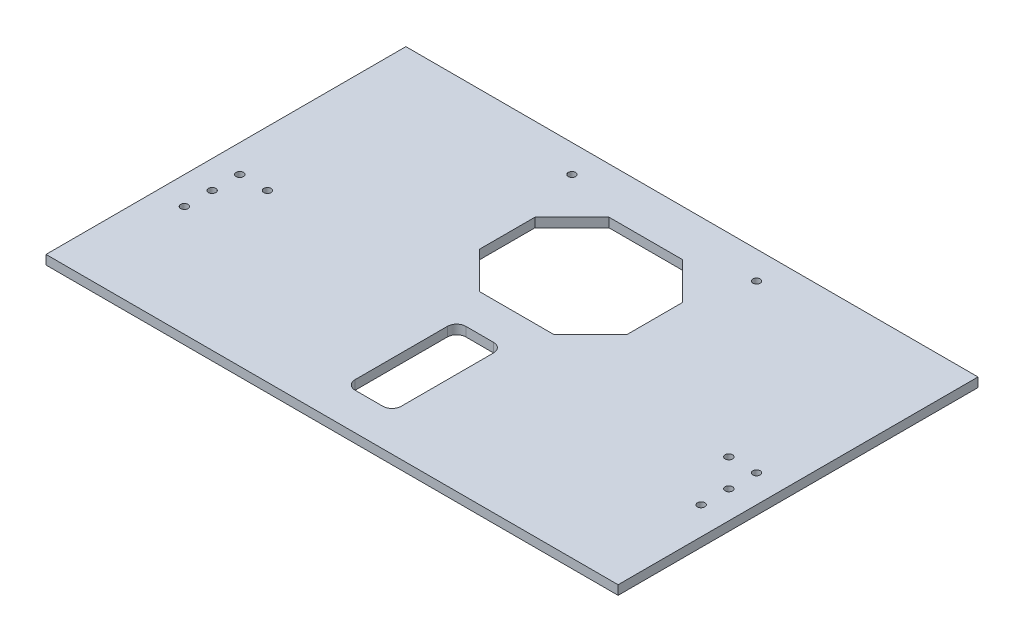
SolidWorks part; units mm, degrees
ref_plane "前视基准面" through (0, 0, 0) normal (0, 0, 1) x (1, 0, 0)
ref_plane "上视基准面" through (0, 0, 0) normal (0, 1, 0) x (1, 0, 0)
ref_plane "右视基准面" through (0, 0, 0) normal (1, 0, 0) x (0, 0, -1)
sketch "Sketch1" plane through (0, 0, 0) normal (0, 1, 0) x (1, 0, 0)
  line L0 (0, 50) -> (0, 97.5) construction
  line L1 (-155, 50) -> (155, 50)
  line L2 (-155, 50) -> (-155, -50)
  line L3 (-155, -50) -> (155, -50)
  line L4 (155, 50) -> (155, -50)
  line L5 (-155, 50) -> (155, -50) construction
  line L6 (-155, -50) -> (155, 50) construction
  line L8 (-60, 145) -> (60, 145)
  line L9 (-60, 145) -> (-60, 50)
  line L10 (-60, 50) -> (60, 50)
  line L11 (60, 145) -> (60, 50)
  line L12 (-60, 145) -> (60, 50) construction
  line L13 (-60, 50) -> (60, 145) construction
  point P0 (0, 0)
  dimension "D1" = 310
  dimension "100" = 100
  dimension "D2" = 120
  dimension "D3" = 95
extrude "Boss-Extrude1" add sketch "Sketch1" along normal blind 5 contours L11 L8 L9 L1 | L4 L1 L2 L3 region at (0, 0, 0) region at (0, 0, -97.5)
sketch "Sketch2" plane through (0, 5, 0) normal (0, 1, 0) x (1, 0, 0)
  line L0 (-140, -50) -> (-140, 50) construction
  line L1 (-155, -50) -> (155, -50) construction
  line L2 (-155, 50) -> (-60, 50) construction
  line L3 (0, 0) -> (0, 145) construction
  line L4 (-60, 145) -> (60, 145) construction
  line L5 (-155, 50) -> (-155, -50) construction
  line L6 (-155, 40) -> (155, 40) construction
  line L7 (-12.5, -30) -> (12.5, -30)
  line L8 (-12.5, -30) -> (-12.5, 30)
  line L9 (-12.5, 30) -> (12.5, 30)
  line L10 (12.5, -30) -> (12.5, 30)
  line L11 (-12.5, -30) -> (12.5, 30) construction
  line L12 (-12.5, 30) -> (12.5, -30) construction
  line L13 (-50, 145) -> (-50, 40) construction
  line L14 (-60, 145) -> (-60, 50) construction
  line L15 (140, -50) -> (140, 50) construction
  line L16 (50, 145) -> (50, 40) construction
  circle A0 centre (-140, 40) radius 2
  circle A2 centre (-125, 40) radius 2
  circle A3 centre (-140, 25) radius 2
  circle A4 centre (-140, 10) radius 2
  circle A5 centre (140, 10) radius 2
  circle A6 centre (140, 25) radius 2
  circle A7 centre (125, 40) radius 2
  circle A8 centre (140, 40) radius 2
  circle A9 centre (-50, 130) radius 2
  circle A10 centre (50, 130) radius 2
  point P26 (0, 40)
  dimension "D6" = 4
  dimension "D7" = 15
  dimension "D8" = 15
  dimension "D9" = 15
  dimension "D10" = 15
  dimension "D11" = 4
  dimension "D1" = 15
  dimension "D2" = 25
  dimension "D3" = 20
  dimension "D4" = 10
  dimension "D5" = 10
extrude "Cut-Extrude1" cut sketch "Sketch2" against normal through all
fillet "Fillet1" radius 5 4 edges at (-12.5, 2.5, 30) (12.5, 2.5, -30) (12.5, 2.5, 30) (-12.5, 2.5, -30)
sketch "Sketch5" plane through (0, 5, 0) normal (0, 1, 0) x (1, 0, 0)
  line L0 (-60, 50) -> (60, 50) construction
  line L1 (0, 50) -> (0, 85) construction
  line L3 (-40, 120) -> (40, 120)
  line L4 (-40, 120) -> (-40, 50)
  line L5 (-40, 50) -> (40, 50)
  line L6 (40, 120) -> (40, 50)
  line L7 (-40, 120) -> (40, 50) construction
  line L8 (-40, 50) -> (40, 120) construction
  line L9 (-60, 145) -> (60, 145) construction
  dimension "D1" = 70
  dimension "D2" = 80
  dimension "D3" = 25
extrude "Cut-Extrude2" cut sketch "Sketch5" against normal blind 5 contours L4 L3 L6 L5
chamfer "Chamfer1" distance 20 angle 45 4 edges at (-40, 2.5, -50) (40, 2.5, -50) (40, 2.5, -120) (-40, 2.5, -120)
sketch "Sketch6" plane through (0, 5, 0) normal (0, 1, 0) x (1, 0, 0)
  line L0 (-60, 145) -> (60, 145) construction
  line L1 (60, 50) -> (155, 50)
  line L2 (60, 50) -> (60, 145)
  line L3 (60, 145) -> (155, 145)
  line L4 (155, 50) -> (155, 145)
  line L5 (155, 50) -> (155, -50) construction
  line L6 (0, 0) -> (0, 145) construction
  line L7 (-155, 50) -> (-155, 145)
  line L8 (-60, 145) -> (-155, 145)
  line L9 (-60, 50) -> (-60, 145)
  line L10 (-60, 50) -> (-155, 50)
extrude "Boss-Extrude2" add sketch "Sketch6" against normal blind 5
